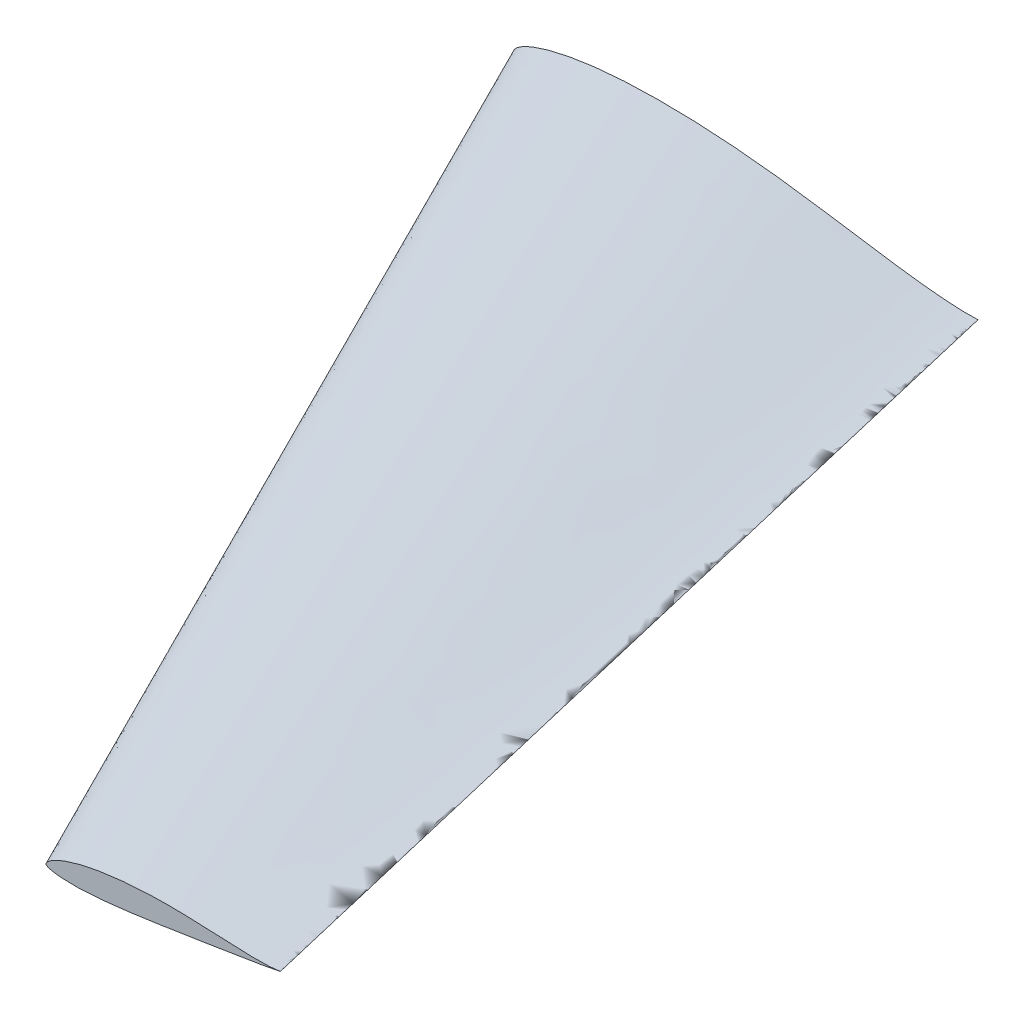
SolidWorks part; units mm, degrees
ref_plane "Front Plane" through (0, 0, 0) normal (0, 0, 1) x (1, 0, 0)
ref_plane "Top Plane" through (0, 0, 0) normal (0, 1, 0) x (1, 0, 0)
ref_plane "Right Plane" through (0, 0, 0) normal (1, 0, 0) x (0, 0, -1)
curve "Curve1"
  spline degree 3 poles (89.4117, -0.0768, 0) (90.1581, 0.0163, 0) (89.3384, -0.0489, 0) (88.6634, -0.0554, 0) (86.9988, -0.0528, 0) (84.9698, 0.0523, 0) (82.3441, 0.2429, 0) (79.2951, 0.5513, 0) (75.8494, 0.9741, 0) (72.0904, 1.4967, 0) (68.0818, 2.0963, 0) (63.8898, 2.7454, 0) (59.5721, 3.4086, 0) (55.1731, 4.0377, 0) (50.7294, 4.6, 0) (46.2733, 5.0781, 0) (41.8379, 5.4578, 0) (37.4583, 5.7341, 0) (33.171, 5.903, 0) (29.014, 5.9637, 0) (25.0243, 5.916, 0) (21.2371, 5.7575, 0) (17.6835, 5.491, 0) (14.3911, 5.12, 0) (11.385, 4.6544, 0) (8.6886, 4.1134, 0) (6.3249, 3.5134, 0) (4.3152, 2.87, 0) (2.6751, 2.2019, 0) (1.4179, 1.5316, 0) (0.6259, 0.9504, 0) (0.2409, 0.5277, 0) (0.0946, 0.3023, 0) (0.0289, 0.1579, 0) (-0.0008, 0.0428, 0) (-0.0021, -0.0493, 0) (0.0369, -0.1348, 0) (0.1141, -0.2351, 0) (0.2404, -0.3544, 0) (0.4668, -0.5223, 0) (1.0037, -0.8427, 0) (2.0204, -1.2501, 0) (3.5765, -1.7042, 0) (5.5485, -2.1302, 0) (7.9154, -2.5093, 0) (10.6594, -2.8252, 0) (13.7595, -3.0666, 0) (17.1926, -3.2314, 0) (20.9311, -3.3172, 0) (24.9437, -3.3283, 0) (29.1943, -3.2696, 0) (33.6423, -3.153, 0) (38.2418, -2.9882, 0) (42.9422, -2.7897, 0) (47.6888, -2.5669, 0) (52.4251, -2.3307, 0) (57.0933, -2.0873, 0) (61.6364, -1.844, 0) (65.999, -1.6043, 0) (70.1278, -1.373, 0) (73.9729, -1.1522, 0) (77.4858, -0.9472, 0) (80.6263, -0.7576, 0) (83.3439, -0.5873, 0) (85.6375, -0.4302, 0) (87.3906, -0.2992, 0) (88.8126, -0.1608, 0) (89.4117, -0.0768, 0) (90.1581, 0.0163, 0) (89.3384, -0.0489, 0) knots -0.013312 -0.00609 -0.00158 0 0.001669 0.006747 0.015187 0.026742 0.041155 0.058129 0.077283 0.098227 0.12058 0.143966 0.168018 0.192451 0.217075 0.24171 0.266182 0.29031 0.313903 0.336767 0.358704 0.37954 0.399122 0.417322 0.434037 0.449154 0.462553 0.474139 0.483848 0.491647 0.497539 0.499898 0.501005 0.501951 0.502492 0.502956 0.503431 0.504004 0.505035 0.506276 0.508636 0.515301 0.524213 0.535296 0.548467 0.563638 0.580726 0.599619 0.62018 0.642246 0.665633 0.690118 0.715452 0.741354 0.76752 0.793634 0.819375 0.844429 0.868488 0.891259 0.912467 0.93185 0.949165 0.964196 0.976755 0.986688 0.99391 0.99842 1 1.001669 1.006747 1.015187 periodic
sketch "CentralProfile" plane through (0, 0, 0) normal (0, 0, 1) x (1, 0, 0)
  line L0 (90, 0) -> (-10, 0) construction
  spline S1 degree 3 poles (89.3464, -0.0853) (90.1757, 0.0181) (89.2649, -0.0544) (88.5149, -0.0616) (86.6653, -0.0586) (84.411, 0.0582) (81.4935, 0.27) (78.1057, 0.6128) (74.2772, 1.0827) (70.1005, 1.6634) (65.6465, 2.3298) (60.9889, 3.051) (56.1914, 3.7881) (51.3037, 4.4871) (46.3662, 5.112) (41.4151, 5.6433) (36.4869, 6.0653) (31.6207, 6.3724) (26.8571, 6.5601) (22.2382, 6.6277) (17.8052, 6.5747) (13.5972, 6.3988) (9.6488, 6.1027) (5.9906, 5.6906) (2.6505, 5.1733) (-0.3455, 4.5723) (-2.9718, 3.9057) (-5.2048, 3.1908) (-7.0272, 2.4486) (-8.4241, 1.7038) (-9.3042, 1.0581) (-9.7319, 0.5884) (-9.8945, 0.3379) (-9.9674, 0.1775) (-10.0005, 0.0496) (-10.0019, -0.0527) (-9.9586, -0.1477) (-9.8728, -0.2592) (-9.7325, -0.3918) (-9.481, -0.5783) (-8.8844, -0.9344) (-7.7548, -1.387) (-6.0258, -1.8916) (-3.8347, -2.365) (-1.2048, -2.7863) (1.844, -3.1373) (5.2887, -3.4056) (9.1032, -3.5888) (13.2571, -3.6842) (17.7154, -3.6966) (22.4383, -3.6314) (27.3806, -3.5021) (32.4911, -3.319) (37.7137, -3.0986) (42.9877, -2.8511) (48.2502, -2.5888) (53.4371, -2.3185) (58.485, -2.0483) (63.3323, -1.782) (67.9199, -1.5251) (72.1922, -1.2798) (76.0954, -1.0522) (79.5848, -0.8416) (82.6044, -0.6524) (85.1527, -0.4778) (87.1006, -0.3324) (88.6806, -0.1786) (89.3464, -0.0853) (90.1757, 0.0181) (89.2649, -0.0544) knots -0.013312 -0.00609 -0.00158 0 0.001669 0.006747 0.015187 0.026742 0.041155 0.058129 0.077283 0.098227 0.12058 0.143966 0.168018 0.192451 0.217075 0.24171 0.266182 0.29031 0.313903 0.336767 0.358704 0.37954 0.399122 0.417322 0.434037 0.449154 0.462553 0.474139 0.483848 0.491647 0.497539 0.499898 0.501005 0.501951 0.502492 0.502956 0.503431 0.504004 0.505035 0.506276 0.508636 0.515301 0.524213 0.535296 0.548467 0.563638 0.580726 0.599619 0.62018 0.642246 0.665633 0.690118 0.715452 0.741354 0.76752 0.793634 0.819375 0.844429 0.868488 0.891259 0.912467 0.93185 0.949165 0.964196 0.976755 0.986688 0.99391 0.99842 1 1.001669 1.006747 1.015187 only from (90, 0) to (90, 0)
  dimension "D1" = 100
ref_plane "CentralProfilePlane" through (0, 0, 0) normal (0, 0, 1) x (1, 0, 0)
curve "Curve2"
  spline degree 3 poles (49.6732, -0.0427, 200) (50.0878, 0.0091, 200) (49.6325, -0.0272, 200) (49.2574, -0.0308, 200) (48.3327, -0.0294, 200) (47.2055, 0.0291, 200) (45.7467, 0.1349, 200) (44.0528, 0.3063, 200) (42.1386, 0.5412, 200) (40.0502, 0.8315, 200) (37.8232, 1.1646, 200) (35.4944, 1.5252, 200) (33.0956, 1.8937, 200) (30.6517, 2.2432, 200) (28.183, 2.5556, 200) (25.7074, 2.8212, 200) (23.2433, 3.0321, 200) (20.8102, 3.1856, 200) (18.4283, 3.2794, 200) (16.1189, 3.3132, 200) (13.9024, 3.2866, 200) (11.7984, 3.1986, 200) (9.8242, 3.0505, 200) (7.9951, 2.8444, 200) (6.325, 2.5858, 200) (4.827, 2.2852, 200) (3.5139, 1.9519, 200) (2.3974, 1.5945, 200) (1.4862, 1.2233, 200) (0.7877, 0.8509, 200) (0.3477, 0.528, 200) (0.1338, 0.2932, 200) (0.0525, 0.1679, 200) (0.0161, 0.0877, 200) (-0.0005, 0.0238, 200) (-0.0012, -0.0274, 200) (0.0205, -0.0749, 200) (0.0634, -0.1306, 200) (0.1336, -0.1969, 200) (0.2593, -0.2902, 200) (0.5576, -0.4682, 200) (1.1224, -0.6945, 200) (1.9869, -0.9468, 200) (3.0825, -1.1835, 200) (4.3974, -1.3941, 200) (5.9219, -1.5695, 200) (7.6442, -1.7037, 200) (9.5515, -1.7952, 200) (11.6284, -1.8429, 200) (13.8576, -1.849, 200) (16.2191, -1.8164, 200) (18.6902, -1.7517, 200) (21.2455, -1.6601, 200) (23.8568, -1.5499, 200) (26.4938, -1.4261, 200) (29.125, -1.2948, 200) (31.7185, -1.1596, 200) (34.2425, -1.0245, 200) (36.6661, -0.8913, 200) (38.9599, -0.7628, 200) (41.0961, -0.6401, 200) (43.0477, -0.5262, 200) (44.7924, -0.4209, 200) (46.3022, -0.3263, 200) (47.5764, -0.239, 200) (48.5503, -0.1662, 200) (49.3403, -0.0893, 200) (49.6732, -0.0427, 200) (50.0878, 0.0091, 200) (49.6325, -0.0272, 200) knots -0.013312 -0.00609 -0.00158 0 0.001669 0.006747 0.015187 0.026742 0.041155 0.058129 0.077283 0.098227 0.12058 0.143966 0.168018 0.192451 0.217075 0.24171 0.266182 0.29031 0.313903 0.336767 0.358704 0.37954 0.399122 0.417322 0.434037 0.449154 0.462553 0.474139 0.483848 0.491647 0.497539 0.499898 0.501005 0.501951 0.502492 0.502956 0.503431 0.504004 0.505035 0.506276 0.508636 0.515301 0.524213 0.535296 0.548467 0.563638 0.580726 0.599619 0.62018 0.642246 0.665633 0.690118 0.715452 0.741354 0.76752 0.793634 0.819375 0.844429 0.868488 0.891259 0.912467 0.93185 0.949165 0.964196 0.976755 0.986688 0.99391 0.99842 1 1.001669 1.006747 1.015187 periodic
ref_plane "OutsideProfilePlane" through (0, 0, 200) normal (0, 0, 1) x (1, 0, 0)
sketch "OutsideProfile" plane through (0, 0, 200) normal (0, 0, 1) x (1, 0, 0)
  line L0 (139.8097, 3.4008) -> (90, -0.957) construction
  line L1 (0, 0) -> (97.907, 0) construction
  spline S1 degree 3 poles (139.4845, 3.3236) (139.8974, 3.4191) (139.4418, 3.335) (139.0638, 3.2922) (138.1307, 3.1971) (136.9874, 3.1384) (135.5047, 3.093) (133.7779, 3.089) (131.8221, 3.1262) (129.685, 3.2011) (127.4034, 3.3047) (125.0163, 3.4254) (122.5578, 3.5467) (120.0558, 3.6442) (117.5326, 3.7017) (115.0073, 3.7112) (112.4993, 3.6668) (110.0286, 3.5677) (107.6159, 3.4137) (105.2824, 3.2067) (103.0491, 2.9486) (100.9356, 2.6401) (98.9593, 2.2847) (97.1355, 1.8858) (95.4777, 1.4505) (93.9978, 0.991) (92.7077, 0.5176) (91.6187, 0.0404) (90.7381, -0.4291) (90.0724, -0.8777) (89.6622, -1.2494) (89.4709, -1.5086) (89.402, -1.6435) (89.3736, -1.7282) (89.3635, -1.7944) (89.3682, -1.8461) (89.395, -1.8918) (89.4441, -1.9436) (89.5218, -2.0031) (89.6584, -2.0841) (89.9779, -2.2325) (90.5714, -2.4019) (91.4699, -2.5662) (92.5998, -2.6906) (93.9484, -2.7658) (95.5047, -2.7837) (97.2563, -2.7392) (99.19, -2.6325) (101.2904, -2.4638) (103.54, -2.2373) (105.9189, -1.9579) (108.4052, -1.6346) (110.9736, -1.2755) (113.5965, -0.8917) (116.244, -0.4916) (118.8849, -0.0845) (121.4872, 0.3226) (124.0194, 0.7224) (126.4507, 1.1098) (128.7514, 1.4788) (130.8937, 1.8256) (132.8507, 2.1442) (134.5999, 2.4326) (136.1132, 2.6856) (137.3896, 2.9067) (138.3645, 3.0818) (139.1535, 3.2418) (139.4845, 3.3236) (139.8974, 3.4191) (139.4418, 3.335) knots -0.013312 -0.00609 -0.00158 0 0.001669 0.006747 0.015187 0.026742 0.041155 0.058129 0.077283 0.098227 0.12058 0.143966 0.168018 0.192451 0.217075 0.24171 0.266182 0.29031 0.313903 0.336767 0.358704 0.37954 0.399122 0.417322 0.434037 0.449154 0.462553 0.474139 0.483848 0.491647 0.497539 0.499898 0.501005 0.501951 0.502492 0.502956 0.503431 0.504004 0.505035 0.506276 0.508636 0.515301 0.524213 0.535296 0.548467 0.563638 0.580726 0.599619 0.62018 0.642246 0.665633 0.690118 0.715452 0.741354 0.76752 0.793634 0.819375 0.844429 0.868488 0.891259 0.912467 0.93185 0.949165 0.964196 0.976755 0.986688 0.99391 0.99842 1 1.001669 1.006747 1.015187 only from (139.8097, 3.4008) to (139.8097, 3.4008)
  point P1 (90, -0.957)
  point P6 (45.5377, -1.3511)
  point P7 (85.4535, -0.957)
  dimension "D1" = 50
  dimension "D2" = 5
  dimension "D3" = 90
ref_axis "Axis3" through (-10, 0, 0) along (0.4472, -0.0043, 0.8944)
loft "Loft3" add profiles "OutsideProfile", "CentralProfile" connector at (89.3795, -1.8639, 200) connector at (-9.9991, -0.023, 0)
mirror "Mirror1" [suppressed] about plane through (0, 0, 0) normal (0, 0, 1)
